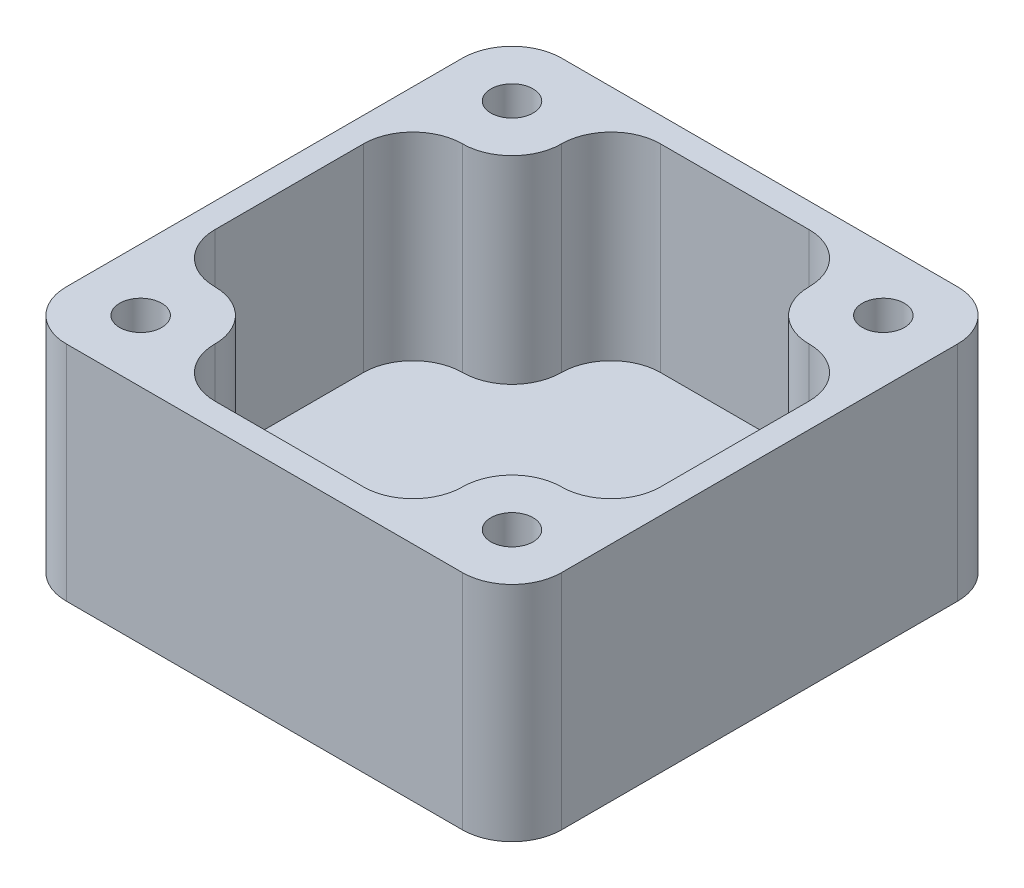
SolidWorks part; units mm, degrees
ref_plane "Front Plane" through (0, 0, 0) normal (0, 0, 1) x (1, 0, 0)
ref_plane "Top Plane" through (0, 0, 0) normal (0, 1, 0) x (1, 0, 0)
ref_plane "Right Plane" through (0, 0, 0) normal (1, 0, 0) x (0, 0, -1)
ref_axis "Axis1" through (0, 18.9, 0) along (0, -1, 0)
sketch "Sketch1" plane through (0, 0, 0) normal (0, 1, 0) x (1, 0, 0)
  line L1 (20, 20) -> (-20, 20)
  line L2 (20, 20) -> (20, -20)
  line L3 (20, -20) -> (-20, -20)
  line L4 (-20, 20) -> (-20, -20)
  line L5 (20, 20) -> (-20, -20) construction
  line L6 (20, -20) -> (-20, 20) construction
  point P0 (0, 0)
  dimension "D1" = 40
extrude "Boss-Extrude1" add sketch "Sketch1" along normal blind 18
sketch "Sketch2" plane through (0, 18, 0) normal (0, 1, 0) x (1, 0, 0)
  line L1 (-15, -15) -> (15, -15) construction
  line L2 (-15, -15) -> (-15, 15) construction
  line L3 (-15, 15) -> (15, 15) construction
  line L4 (15, -15) -> (15, 15) construction
  line L5 (-15, -15) -> (15, 15) construction
  line L6 (-15, 15) -> (15, -15) construction
  circle A0 centre (15, 15) radius 1.7
  circle A1 centre (15, -15) radius 1.7
  circle A2 centre (-15, -15) radius 1.7
  circle A3 centre (-15, 15) radius 1.7
  point P0 (0, 0)
  point P11 (-15.2877, -15)
  dimension "D2" = 3.4
  dimension "D1" = 30
extrude "Cut-Extrude1" cut sketch "Sketch2" against normal through all
sketch "Sketch3" plane through (0, 18, 0) normal (0, 1, 0) x (1, 0, 0)
  line L0 (20, -20) -> (20, 20) construction
  line L1 (-18, -10) -> (18, -10)
  line L2 (-18, -10) -> (-18, 10)
  line L3 (-18, 10) -> (18, 10)
  line L4 (18, -10) -> (18, 10)
  line L5 (-18, -10) -> (18, 10) construction
  line L6 (-18, 10) -> (18, -10) construction
  line L7 (15, -13.3) -> (15, -10) construction
  line L9 (15, -16.7) -> (15, -20) construction
  line L10 (-20, -20) -> (20, -20) construction
  circle A1 centre (15, -15) radius 1.7 construction
  point P0 (0, 0)
  point P17 (0, 0)
  dimension "D1" = 2
extrude "Cut-Extrude2" cut sketch "Sketch3" against normal offset from surface (16 mm away) 2 up to face at (-15, 0, -13.3)
pattern_circular "CirPattern1" count 2 every 90 about axis through (0, 18.9, 0) along (0, -1, 0) of "Cut-Extrude2"
fillet "Fillet1" radius 4 16 edges at (20, 9, -20) (-20, 9, -20) (-20, 9, 20) (20, 9, 20) (-10, 10, 18) (-10, 10, 10) (-18, 10, 10) (-18, 10, -10) (-10, 10, -10) (-10, 10, -18) (10, 10, -18) (10, 10, -10) (18, 10, -10) (18, 10, 10) (10, 10, 18) (10, 10, 10)
